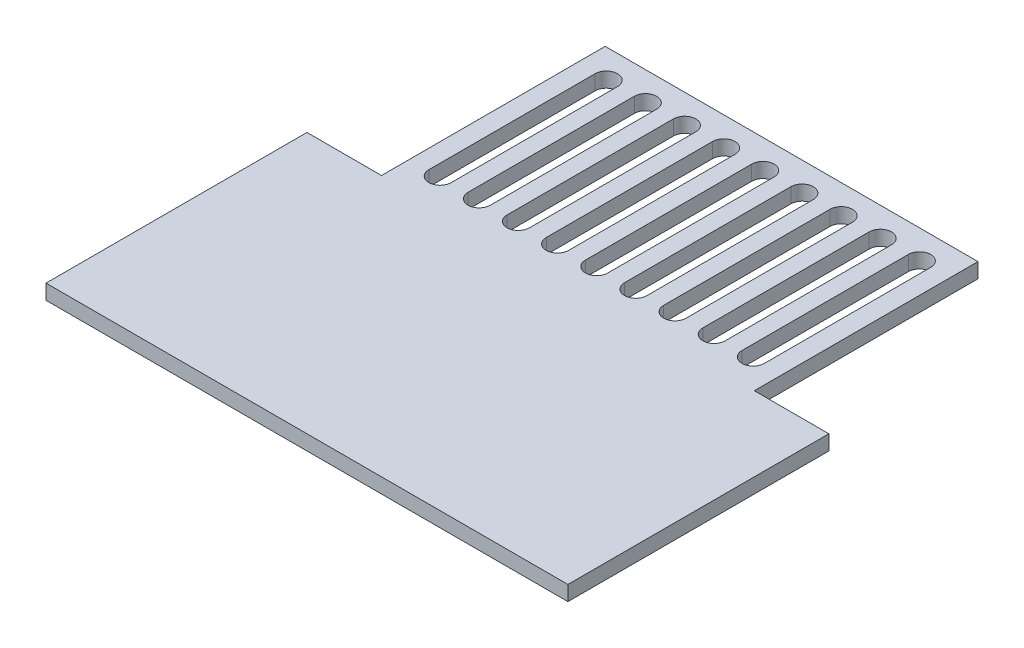
SolidWorks part; units mm, degrees
material "6061-T6 (SS)"
ref_plane "Front Plane" through (0, 0, 0) normal (0, 0, 1) x (1, 0, 0)
ref_plane "Top Plane" through (0, 0, 0) normal (0, 1, 0) x (1, 0, 0)
ref_plane "Right Plane" through (0, 0, 0) normal (1, 0, 0) x (0, 0, -1)
sketch "Sketch2" plane through (0, 0, 0) normal (0, 1, 0) x (1, 0, 0)
  line L0 (0, 65) -> (0, 35) construction
  line L1 (-35, 35) -> (-25, 35)
  line L2 (-35, 35) -> (-35, 0)
  line L3 (-35, 0) -> (35, 0)
  line L4 (35, 35) -> (35, 0)
  line L7 (5.25, 38.8472) -> (5.25, 61.1528) construction
  line L8 (-25, 35) -> (-25, 65)
  line L9 (-25, 65) -> (25, 65)
  line L10 (25, 35) -> (25, 65)
  line L11 (0, 38.8472) -> (0, 61.1528) construction
  line L12 (-1.5, 38.8472) -> (-1.5, 61.1528)
  line L13 (1.5, 38.8472) -> (1.5, 61.1528)
  line L14 (25, 35) -> (35, 35)
  line L15 (3.75, 38.8472) -> (3.75, 61.1528)
  line L16 (6.75, 38.8472) -> (6.75, 61.1528)
  line L17 (10.5, 38.8472) -> (10.5, 61.1528) construction
  line L18 (9, 38.8472) -> (9, 61.1528)
  line L19 (12, 38.8472) -> (12, 61.1528)
  line L20 (15.75, 38.8472) -> (15.75, 61.1528) construction
  line L21 (14.25, 38.8472) -> (14.25, 61.1528)
  line L22 (17.25, 38.8472) -> (17.25, 61.1528)
  line L23 (21, 38.8472) -> (21, 61.1528) construction
  line L24 (19.5, 38.8472) -> (19.5, 61.1528)
  line L25 (22.5, 38.8472) -> (22.5, 61.1528)
  line L26 (-5.25, 38.8472) -> (-5.25, 61.1528) construction
  line L27 (-6.75, 38.8472) -> (-6.75, 61.1528)
  line L28 (-3.75, 38.8472) -> (-3.75, 61.1528)
  line L29 (-10.5, 38.8472) -> (-10.5, 61.1528) construction
  line L30 (-12, 38.8472) -> (-12, 61.1528)
  line L31 (-9, 38.8472) -> (-9, 61.1528)
  line L32 (-15.75, 38.8472) -> (-15.75, 61.1528) construction
  line L33 (-17.25, 38.8472) -> (-17.25, 61.1528)
  line L34 (-14.25, 38.8472) -> (-14.25, 61.1528)
  line L35 (-21, 38.8472) -> (-21, 61.1528) construction
  line L36 (-22.5, 38.8472) -> (-22.5, 61.1528)
  line L37 (-19.5, 38.8472) -> (-19.5, 61.1528)
  arc A0 (-1.5, 38.8472) -> (1.5, 38.8472) centre (0, 38.8472) ccw
  arc A1 (1.5, 61.1528) -> (-1.5, 61.1528) centre (0, 61.1528) ccw
  arc A2 (3.75, 38.8472) -> (6.75, 38.8472) centre (5.25, 38.8472) ccw
  arc A3 (6.75, 61.1528) -> (3.75, 61.1528) centre (5.25, 61.1528) ccw
  arc A4 (9, 38.8472) -> (12, 38.8472) centre (10.5, 38.8472) ccw
  arc A5 (12, 61.1528) -> (9, 61.1528) centre (10.5, 61.1528) ccw
  arc A6 (14.25, 38.8472) -> (17.25, 38.8472) centre (15.75, 38.8472) ccw
  arc A7 (17.25, 61.1528) -> (14.25, 61.1528) centre (15.75, 61.1528) ccw
  arc A8 (19.5, 38.8472) -> (22.5, 38.8472) centre (21, 38.8472) ccw
  arc A9 (22.5, 61.1528) -> (19.5, 61.1528) centre (21, 61.1528) ccw
  arc A10 (-6.75, 38.8472) -> (-3.75, 38.8472) centre (-5.25, 38.8472) ccw
  arc A11 (-3.75, 61.1528) -> (-6.75, 61.1528) centre (-5.25, 61.1528) ccw
  arc A12 (-12, 38.8472) -> (-9, 38.8472) centre (-10.5, 38.8472) ccw
  arc A13 (-9, 61.1528) -> (-12, 61.1528) centre (-10.5, 61.1528) ccw
  arc A14 (-17.25, 38.8472) -> (-14.25, 38.8472) centre (-15.75, 38.8472) ccw
  arc A15 (-14.25, 61.1528) -> (-17.25, 61.1528) centre (-15.75, 61.1528) ccw
  arc A16 (-22.5, 38.8472) -> (-19.5, 38.8472) centre (-21, 38.8472) ccw
  arc A17 (-19.5, 61.1528) -> (-22.5, 61.1528) centre (-21, 61.1528) ccw
  point P0 (0, 0)
  point P13 (0, 50)
  point P22 (5.25, 50)
  point P29 (10.5, 50)
  point P37 (15.75, 50)
  point P44 (21, 50)
  point P50 (-5.25, 50)
  point P57 (-10.5, 50)
  point P64 (-15.75, 50)
  point P71 (-21, 50)
  dimension "D5" = 3
  dimension "D6" = 5
  dimension "D7" = 5
  dimension "D1" = 35
  dimension "D2" = 70
  dimension "D3" = 50
  dimension "D4" = 30
extrude "Boss-Extrude1" add sketch "Sketch2" along normal blind 2
sketch "Sketch4" plane through (0, 0, 0) normal (0, -1, 0) x (1, 0, 0)
  line L0 (42.5, 0) -> (35, 7.5)
  line L1 (-35, 0) -> (35, 0) construction
  line L2 (35, 0) -> (35, -35) construction
  line L3 (42.5, 0) -> (35, 0)
  line L4 (35, 0) -> (35, 7.5)
  line L5 (0, -17.5) -> (1.77, -17.5) construction
  line L6 (39.3934, -7.5) -> (27.5, 4.3934)
  line L7 (27.5, 4.3934) -> (27.5, -12.5)
  line L8 (27.5, -12.5) -> (5, -12.5)
  line L9 (5, -12.5) -> (5, -7.5)
  line L10 (5, -7.5) -> (39.3934, -7.5)
  line L11 (0, -65) -> (0, 0) construction
  line L13 (-35, -17.5) -> (35, -17.5) construction
  line L14 (-35, -35) -> (-35, 0) construction
  point P16 (0, -65)
  point P23 (0, 0)
  dimension "D1" = 45
  dimension "D2" = 7.5
  dimension "D3" = 7.5
  dimension "D4" = 5
  dimension "D5" = 5
  dimension "D6" = 7.5
  dimension "D7" = 25
extrude "Cut-Extrude1" cut sketch "Sketch4" against normal up to surface (2 mm away) rebuild error yes up to face at (0, 2, -33.75)
sketch "Sketch5" plane through (0, 0, 0) normal (1, 0, 0) x (0, 0, -1)
  line L0 (0, -0.174) -> (0, 0.9435) construction
pattern_circular "CirPattern1" count 4 over 360 about axis through (0, -0.174, 0) along (0, 1, 0) rebuild error yes reverse direction yes
